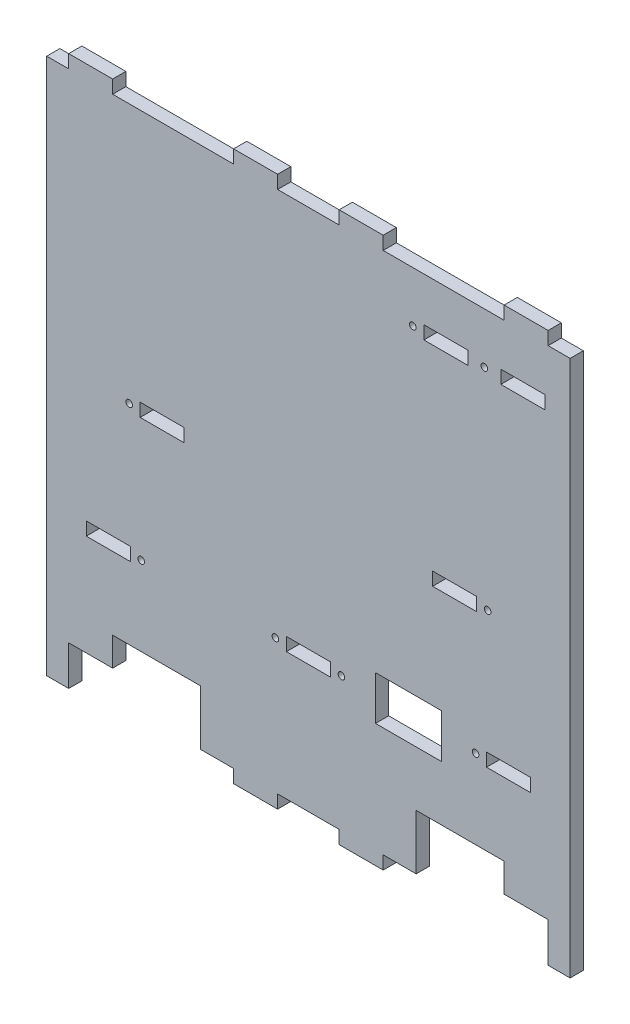
SolidWorks part; units mm, degrees
ref_plane "Plan de face" through (0, 0, 0) normal (0, 0, 1) x (1, 0, 0)
ref_plane "Plan de dessus" through (0, 0, 0) normal (0, 1, 0) x (1, 0, 0)
ref_plane "Plan de droite" through (0, 0, 0) normal (1, 0, 0) x (0, 0, -1)
sketch "Esquisse1" plane through (0, 0, 0) normal (0, 0, 1) x (1, 0, 0)
  line L0 (0, 139.6766) -> (0, -178.3461) construction
  line L1 (-109, 119) -> (109, 119)
  line L2 (-109, 119) -> (-109, -119)
  line L3 (-109, -119) -> (109, -119)
  line L4 (109, 119) -> (109, -119)
  line L5 (-101, -61) -> (-81, -61)
  line L6 (-101, -61) -> (-101, -55)
  line L7 (-101, -55) -> (-81, -55)
  line L8 (-81, -61) -> (-81, -55)
  line L9 (-10, -61) -> (10, -61)
  line L10 (-10, -61) -> (-10, -55)
  line L11 (-10, -55) -> (10, -55)
  line L12 (10, -61) -> (10, -55)
  line L13 (81, -61) -> (101, -61)
  line L14 (81, -61) -> (81, -55)
  line L15 (81, -55) -> (101, -55)
  line L16 (101, -61) -> (101, -55)
  line L17 (-76.5, 4) -> (-56.5, 4)
  line L18 (-76.5, 4) -> (-76.5, -2)
  line L19 (-76.5, -2) -> (-56.5, -2)
  line L20 (-56.5, 4) -> (-56.5, -2)
  line L21 (56.5, 4) -> (76.5, 4)
  line L22 (56.5, 4) -> (56.5, -2)
  line L23 (56.5, -2) -> (76.5, -2)
  line L24 (76.5, 4) -> (76.5, -2)
  line L25 (30.5, -69) -> (60.5, -69)
  line L26 (30.5, -69) -> (30.5, -49)
  line L27 (30.5, -49) -> (60.5, -49)
  line L28 (60.5, -69) -> (60.5, -49)
  line L30 (52.5, 99) -> (72.5, 99)
  line L31 (52.5, 99) -> (52.5, 93)
  line L32 (52.5, 93) -> (72.5, 93)
  line L33 (72.5, 99) -> (72.5, 93)
  line L34 (87.5, 99) -> (107.5, 99)
  line L35 (87.5, 99) -> (87.5, 93)
  line L36 (87.5, 93) -> (107.5, 93)
  line L37 (107.5, 99) -> (107.5, 93)
  dimension "D1" = 238
  dimension "D2" = 218
  dimension "D3" = 109
  dimension "D4" = 119
  dimension "D5" = 20
  dimension "D6" = 6
  dimension "D7" = 6
  dimension "D8" = 20
  dimension "D9" = 20
  dimension "D10" = 6
  dimension "D11" = 58
  dimension "D12" = 8
  dimension "D13" = 8
  dimension "D14" = 99
  dimension "D15" = 58
  dimension "D16" = 58
  dimension "D17" = 20
  dimension "D18" = 6
  dimension "D19" = 6
  dimension "D20" = 20
  dimension "D21" = 117
  dimension "D22" = 117
  dimension "D23" = 32.5
  dimension "D24" = 32.5
  dimension "D25" = 20
  dimension "D26" = 30
  dimension "D27" = 50
  dimension "D28" = 20.5
  dimension "D29" = 6
  dimension "D30" = 6
  dimension "D31" = 20
  dimension "D32" = 20
  dimension "D33" = 20
  dimension "D34" = 20
  dimension "D35" = 15
  dimension "D36" = 1.5
extrude "Boss.-Extru.1" add sketch "Esquisse1" along normal blind 6
sketch "Esquisse2" plane through (0, 0, 6) normal (0, 0, 1) x (1, 0, 0)
  line L0 (-109, -119) -> (109, -119) construction
  line L1 (-89, -119) -> (-49, -119)
  line L2 (-89, -119) -> (-89, -94)
  line L3 (-89, -94) -> (-49, -94)
  line L4 (-49, -119) -> (-49, -94)
  line L5 (-109, 119) -> (-109, -119) construction
  line L6 (49, -119) -> (89, -119)
  line L7 (49, -119) -> (49, -94)
  line L8 (49, -94) -> (89, -94)
  line L9 (89, -119) -> (89, -94)
  line L10 (109, -119) -> (109, 119) construction
  dimension "D1" = 40
  dimension "D2" = 20
  dimension "D3" = 40
  dimension "D4" = 20
  dimension "D5" = 25
  dimension "D6" = 25
extrude "Enlèv. mat.-Extru.1" cut sketch "Esquisse2" against normal blind 6
sketch "Esquisse3" plane through (0, 0, 6) normal (0, 0, 1) x (1, 0, 0)
  line L0 (0, 157.5653) -> (0, -190.6765) construction
  line L5 (-49, -119) -> (49, -119) construction
  line L6 (-34, -119) -> (-14, -119)
  line L7 (-34, -119) -> (-34, -125)
  line L8 (-34, -125) -> (-14, -125)
  line L9 (-14, -119) -> (-14, -125)
  line L10 (-49, -119) -> (-49, -94) construction
  line L15 (14, -119) -> (14, -125)
  line L16 (34, -125) -> (14, -125)
  line L17 (34, -119) -> (34, -125)
  line L18 (34, -119) -> (14, -119)
  line L19 (198.2674, 0) -> (-212.4835, 0) construction
  line L20 (0, -157.5653) -> (0, 190.6765) construction
  line L21 (34, 125) -> (14, 125)
  line L22 (14, 119) -> (14, 125)
  line L23 (89, 125) -> (109, 125)
  line L24 (89, 125) -> (89, 119)
  line L25 (89, 119) -> (109, 119)
  line L26 (109, 125) -> (109, 119)
  line L27 (-14, 119) -> (-14, 125)
  line L28 (-34, 125) -> (-14, 125)
  line L29 (-34, 119) -> (-34, 125)
  line L30 (-34, 119) -> (-14, 119)
  line L31 (-109, 125) -> (-109, 119)
  line L32 (-89, 119) -> (-109, 119)
  line L33 (-89, 125) -> (-89, 119)
  line L34 (-89, 125) -> (-109, 125)
  line L35 (34, 119) -> (14, 119)
  line L36 (34, 119) -> (34, 125)
  dimension "D2" = 20
  dimension "D3" = 6
  dimension "D4" = 15
extrude "Boss.-Extru.3" add sketch "Esquisse3" against normal blind 6
sketch "Esquisse4" plane through (0, 0, 6) normal (0, 0, 1) x (1, 0, 0)
  line L0 (-111.0944, 1) -> (126.4062, 1) construction
  line L1 (116.6655, -58) -> (-122.9189, -58) construction
  line L2 (76.5, -2) -> (76.5, 4) construction
  line L3 (0, 153.5677) -> (0, -173.1111) construction
  line L4 (45.0686, 96) -> (109.1297, 96) construction
  line L5 (81, -55) -> (81, -61) construction
  line L6 (10, -61) -> (10, -55) construction
  line L7 (-10, -55) -> (-10, -61) construction
  line L8 (72.5, 93) -> (72.5, 99) construction
  line L12 (52.5, 99) -> (52.5, 93) construction
  line L13 (52.5, 93) -> (72.5, 93) construction
  circle A0 centre (-15, -58) radius 1.5
  circle A1 centre (-76, -58) radius 1.5
  circle A2 centre (80, 96) radius 1.5
  circle A3 centre (81.5, 1) radius 1.5
  circle A4 centre (76, -58) radius 1.5
  circle A5 centre (15, -58) radius 1.5
  circle A6 centre (-81.5, 1) radius 1.5
  circle A7 centre (47.5, 96) radius 1.5
  dimension "D2" = 5
  dimension "D3" = 3
  dimension "D4" = 3
  dimension "D5" = 5
  dimension "D6" = 5
  dimension "D7" = 3
  dimension "D8" = 3
  dimension "D9" = 3
  dimension "D10" = 5
  dimension "D11" = 3
  dimension "D12" = 7.5
  dimension "D13" = 5
  dimension "D14" = 3
extrude "Enlèv. mat.-Extru.2" cut sketch "Esquisse4" against normal blind 6
sketch "Esquisse5" plane through (0, 0, 6) normal (0, 0, 1) x (1, 0, 0)
  line L0 (-109, 119) -> (-109, -125)
  line L1 (-109, 119) -> (-119, 119)
  line L2 (-109, -125) -> (-119, -125)
  line L3 (-119, 119) -> (-119, -125)
  line L5 (109, -125) -> (109, 119)
  line L6 (109, -125) -> (119, -125)
  line L7 (109, 119) -> (119, 119)
  line L8 (119, -125) -> (119, 119)
  line L11 (109, 125) -> (89, 125) construction
  line L12 (-89, 125) -> (-109, 125) construction
  dimension "D1" = 10
  dimension "D2" = 10
  dimension "D3" = 244
  dimension "D4" = 244
  dimension "D5" = 6
  dimension "D6" = 6
extrude "Boss.-Extru.4" add sketch "Esquisse5" against normal blind 6
sketch "Esquisse6" plane through (0, 0, 6) normal (0, 0, 1) x (1, 0, 0)
  line L0 (0, 108.4917) -> (0, -172.5759) construction
  line L1 (89, -119) -> (109, -119)
  line L2 (89, -119) -> (89, -107)
  line L3 (89, -107) -> (109, -107)
  line L4 (109, -119) -> (109, -107)
  line L5 (-109, -119) -> (-109, -107)
  line L6 (-89, -107) -> (-109, -107)
  line L7 (-89, -119) -> (-89, -107)
  line L8 (-89, -119) -> (-109, -119)
  dimension "D1" = 12
  dimension "D2" = 20
extrude "Enlèv. mat.-Extru.3" cut sketch "Esquisse6" against normal blind 6
equation "\"D3@Esquisse1\"=\"D2@Esquisse1\"/2"
equation "\"D4@Esquisse1\"=\"D1@Esquisse1\"/2"
